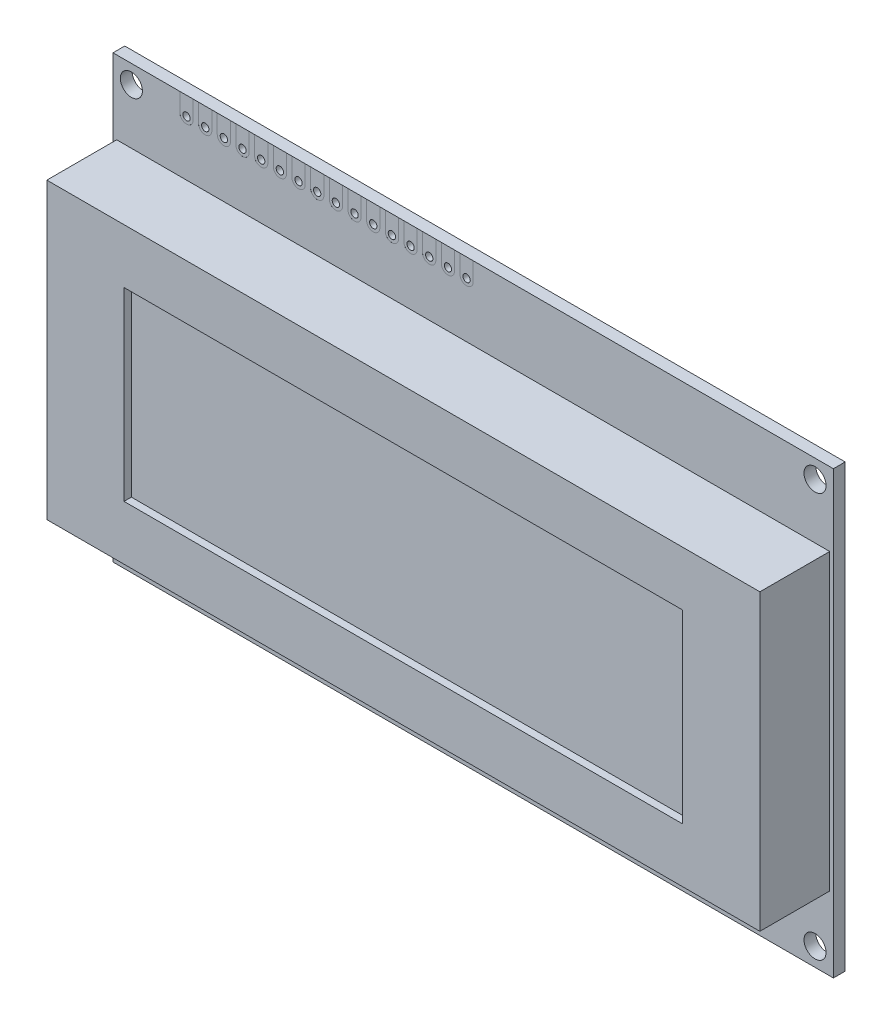
SolidWorks part; units mm, degrees
ref_plane "Alzado" through (0, 0, 0) normal (0, 0, 1) x (1, 0, 0)
ref_plane "Planta" through (0, 0, 0) normal (0, 1, 0) x (1, 0, 0)
ref_plane "Vista lateral" through (0, 0, 0) normal (1, 0, 0) x (0, 0, -1)
sketch "Croquis1" plane through (0, 0, 0) normal (0, 0, 1) x (1, 0, 0)
  line L1 (-49, 30) -> (49, 30)
  line L2 (-49, 30) -> (-49, -30)
  line L3 (-49, -30) -> (49, -30)
  line L4 (49, 30) -> (49, -30)
  point P4 (0, 30)
  point P6 (-49, 0)
  dimension "D1" = 60
  dimension "D2" = 98
extrude "Saliente-Extruir1" add sketch "Croquis1" along normal mid plane 1.6
sketch "Croquis2" plane through (0, 0, 0.8) normal (0, 0, 1) x (1, 0, 0)
  line L1 (-46.5, 27.5) -> (46.5, 27.5) construction
  line L2 (-46.5, 27.5) -> (-46.5, -27.5) construction
  line L3 (-46.5, -27.5) -> (46.5, -27.5) construction
  line L4 (46.5, 27.5) -> (46.5, -27.5) construction
  circle A0 centre (-46.5, 27.5) radius 1.5
  circle A1 centre (-46.5, -27.5) radius 1.5
  circle A2 centre (46.5, -27.5) radius 1.5
  circle A3 centre (46.5, 27.5) radius 1.5
  point P10 (46.5, 0)
  point P12 (0, 27.5)
  dimension "D3" = 3
  dimension "D1" = 55
  dimension "D2" = 93
extrude "Cortar-Extruir1" cut sketch "Croquis2" against normal through all
sketch "Croquis3" plane through (0, 0, 0.8) normal (0, 0, 1) x (1, 0, 0)
  line L1 (-48.5, 20) -> (48.5, 20)
  line L2 (-48.5, 20) -> (-48.5, -20)
  line L3 (-48.5, -20) -> (48.5, -20)
  line L4 (48.5, 20) -> (48.5, -20)
  point P4 (0, 20)
  point P6 (-48.5, 0)
  dimension "D1" = 40
  dimension "D2" = 97
extrude "Saliente-Extruir2" add sketch "Croquis3" along normal blind 9.5
sketch "Croquis4" plane through (0, 0, 10.3) normal (0, 0, 1) x (1, 0, 0)
  line L1 (-38, 12.6) -> (38, 12.6)
  line L2 (-38, 12.6) -> (-38, -12.6)
  line L3 (-38, -12.6) -> (38, -12.6)
  line L4 (38, 12.6) -> (38, -12.6)
  point P4 (0, 12.6)
  point P6 (-38, 0)
  dimension "D1" = 76
  dimension "D2" = 25.2
extrude "Cortar-Extruir2" cut sketch "Croquis4" against normal blind 1
sketch "Croquis5" plane through (0, 0, 9.3) normal (0, 0, 1) x (1, 0, 0)
  line L0 (49, 30) -> (-49, 30) construction
  line L1 (-39.9, 30) -> (-38.1, 30)
  line L2 (-39.9, 30) -> (-39.9, 27.5)
  line L3 (-49, 30) -> (-49, -30) construction
  line L4 (-38.1, 30) -> (-38.1, 27.5)
  arc A0 (-39.9, 27.5) -> (-38.1, 27.5) centre (-39, 27.5) ccw
  circle A1 centre (-39, 27.5) radius 0.5
  dimension "D1" = 1
  dimension "D2" = 10
  dimension "D3" = 2.5
  dimension "D4" = 1.8
extrude "Cortar-Extruir5" cut sketch "Croquis5" against normal blind 0.001 from surface starting at face at (-45, -27.5, 0.8)
extrude "Cortar-Extruir6" cut sketch "Croquis5<2>" against normal through all contours A1 region at (-39, 27.5, 9.3)
sketch "Croquis5<2>" plane through (0, 0, 9.3) normal (0, 0, 1) x (1, 0, 0) same geometry as "Croquis5"
pattern_linear "MatrizL1" count 16 spacing 2.54 along (1, 0, 0) of "Cortar-Extruir5", "Cortar-Extruir6"
